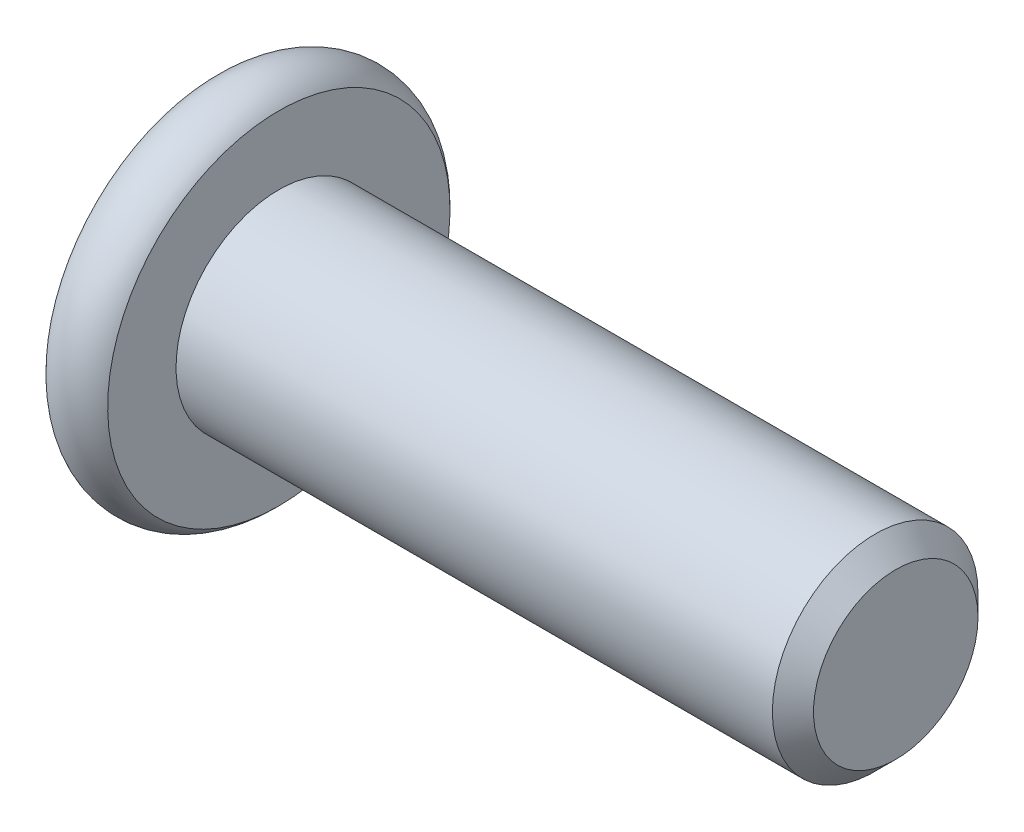
SolidWorks part; units mm, degrees
material "Plain Carbon Steel"
ref_plane "Front Plane" through (0, 0, 0) normal (0, 0, 1) x (1, 0, 0)
ref_plane "Top Plane" through (0, 0, 0) normal (0, 1, 0) x (1, 0, 0)
ref_plane "Right Plane" through (0, 0, 0) normal (1, 0, 0) x (0, 0, -1)
other "M5 x 15"
sketch "Sketch2" plane through (0, 0, 0) normal (1, 0, 0) x (0, 0, -1)
  circle A0 centre (0, 0) radius 2.5
  dimension "D1" = 5
extrude "Boss-Extrude1" add sketch "Sketch2" against normal blind 15
chamfer "Chamfer1" distance 0.5 angle 45 1 edges at (0, 0, -2.5)
sketch "Sketch6" plane through (0, 0, 0) normal (0, 0, 1) x (1, 0, 0)
  line L0 (-16.5, 0) -> (-16.5, 4.1614)
  line L1 (-16.5, 0) -> (-15, 0)
  line L2 (-15.75, 0) -> (-15.75, 3.5) construction
  line L6 (-15, 4.1614) -> (-15, 0)
  line L8 (-15, 0) -> (-14.6471, 0) construction
  line L10 (-15, 2.5) -> (-15, -2.5) construction
  arc A0 (-16.5, 4.1614) -> (-15, 4.1614) centre (-15.75, 3.5) cw
  dimension "D3" = 1
  dimension "D1" = 1.5
  dimension "D2" = 9
revolve "Revolve1" add sketch "Sketch6" angle 360 about L8
sketch "Sketch7" plane through (-16.5, 0, 0) normal (-1, 0, 0) x (0, 0, 1)
  line L1 (0, 1.7321) -> (-1.5, 0.866)
  line L2 (-1.5, 0.866) -> (-1.5, -0.866)
  line L3 (-1.5, -0.866) -> (0, -1.7321)
  line L4 (0, -1.7321) -> (1.5, -0.866)
  line L5 (1.5, -0.866) -> (1.5, 0.866)
  line L6 (1.5, 0.866) -> (0, 1.7321)
  circle A0 centre (0, 0) radius 1.5 construction
  dimension "D1" = 3
extrude "Cut-Extrude1" cut sketch "Sketch7" against normal blind 2.3
sketch "Sketch8" plane through (-16.5, 0, 0) normal (-1, 0, 0) x (0, 0, 1)
  circle A0 centre (0, 0) radius 1.7821
  dimension "D1" = 0.05
extrude "Cut-Extrude2" cut sketch "Sketch8" against normal blind 1 draft 45
